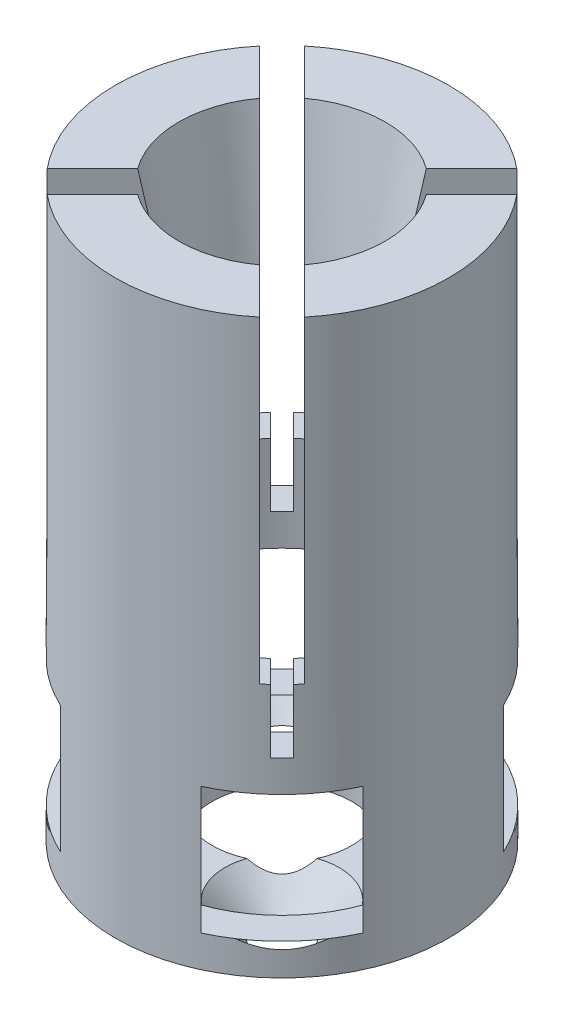
SolidWorks part; units mm, degrees
ref_plane "Front Plane" through (0, 0, 0) normal (0, 0, 1) x (1, 0, 0)
ref_plane "Top Plane" through (0, 0, 0) normal (0, 1, 0) x (1, 0, 0)
ref_plane "Right Plane" through (0, 0, 0) normal (1, 0, 0) x (0, 0, -1)
sketch "Sketch1" plane through (0, 0, 0) normal (0, 1, 0) x (1, 0, 0)
  circle A0 centre (0, 0) radius 16.6687
  dimension "D1" = 33.3375
extrude "Boss-Extrude1" add sketch "Sketch1" along normal blind 3.175 contours A0
sketch "Sketch2" plane through (0, 3.175, 0) normal (0, 1, 0) x (1, 0, 0)
  circle A0 centre (0, 0) radius 16.6687
  circle A1 centre (0, 0) radius 13.4938
  circle A2 centre (0, 0) radius 16.6687 construction
  dimension "D2" = 3.175
extrude "Boss-Extrude2" add sketch "Sketch2" along normal blind 53.975
ref_axis "Axis1" through (0, 57.15, 0) along (0, -1, 0)
ref_plane "Plane1" through (0, 0, 0) normal (-0.7071, 0, 0.7071) x (0, -1, 0)
ref_plane "Plane2" through (0, 31.75, 0) normal (0, 1, 0) x (1, 0, 0)
ref_plane "Plane3" through (0, 57.15, 0) normal (0, 1, 0) x (1, 0, 0)
sketch "Sketch7" plane through (0, 0, 0) normal (0, -1, 0) x (1, 0, 0)
  circle A0 centre (0, 0) radius 6.985
  dimension "D1" = 13.97
extrude "Cut-Extrude1" cut sketch "Sketch7" against normal through all
sketch "Sketch12" plane through (0, 31.75, 0) normal (0, 1, 0) x (1, 0, 0)
  circle A0 centre (0, 0) radius 14.2875
  dimension "D1" = 28.575
extrude "Boss-Extrude7" add sketch "Sketch12" along normal blind 25.4 contours A0
sketch "Sketch10" plane through (0, 57.15, 0) normal (0, 1, 0) x (1, 0, 0)
  circle A0 centre (0, 0) radius 10.32
  dimension "D1" = 20.64
sketch "Sketch11" plane through (0, 31.75, 0) normal (0, 1, 0) x (1, 0, 0)
  circle A0 centre (0, 0) radius 6.35
  dimension "D1" = 12.7
loft "Cut-Loft2" cut profiles "Sketch10", "Sketch11" connector at (-0.5056, 57.15, -10.3076) connector at (-3.3654, 31.75, -5.3849)
sketch "Sketch9" plane through (0, 0, 0) normal (-0.7071, 0, 0.7071) x (0, -1, 0)
  line L5 (-3.1775, -5.715) -> (-15.8775, -5.715)
  line L6 (-19.05, -0.8001) -> (-25.4, -0.8001)
  line L7 (-25.4, -1.5875) -> (-177.8, -1.5875)
  line L8 (-25.4, -1.5875) -> (-25.4, 1.5875)
  line L9 (-25.4, 1.5875) -> (-177.8, 1.5875)
  line L10 (-177.8, -1.5875) -> (-177.8, 1.5875)
  line L11 (-25.4, -1.5875) -> (-177.8, 1.5875) construction
  line L12 (-25.4, 1.5875) -> (-177.8, -1.5875) construction
  line L13 (-19.05, -0.8001) -> (-19.05, 0.8001)
  line L14 (-19.05, 0.8001) -> (-25.4, 0.8001)
  line L15 (-25.4, -0.8001) -> (-25.4, 0.8001)
  line L16 (-19.05, -0.8001) -> (-25.4, 0.8001) construction
  line L17 (-19.05, 0.8001) -> (-25.4, -0.8001) construction
  line L18 (-57.15, 0) -> (-3.175, 0) construction
  line L19 (-3.1775, -5.715) -> (-3.1775, 5.715)
  line L20 (-3.1775, 5.715) -> (-15.8775, 5.715)
  line L21 (-15.8775, -5.715) -> (-15.8775, 5.715)
  line L22 (-3.1775, -5.715) -> (-15.8775, 5.715) construction
  line L23 (-3.1775, 5.715) -> (-15.8775, -5.715) construction
  line L24 (0, -16.6688) -> (0, 16.6688) construction
  point P4 (-22.225, 0)
  point P9 (-101.6, 0)
  point P16 (-9.5275, 0)
  dimension "D1" = 3.175
  dimension "D2" = 25.4
  dimension "D3" = 1.6002
  dimension "D4" = 6.35
  dimension "D5" = 152.4
  dimension "D6" = 11.43
  dimension "D7" = 12.7
  dimension "D8" = 3.1775
extrude "Cut-Extrude2" cut sketch "Sketch9" against normal up to next contours L7 L10 L9 L8 | L6 L15 L14 L13 | L19 L5 L21 L20
pattern_circular "CirPattern2" count 4 over 360 about axis through (0, 0, 0) along (0, 1, 0) of "Cut-Extrude2"
sketch "Sketch5" plane through (0, 0, 0) normal (0, -1, 0) x (1, 0, 0)
  line L0 (-8.255, 8.255) -> (8.255, -8.255) construction
  line L1 (8.255, -8.255) -> (8.255, 8.255) construction
  line L2 (8.255, 8.255) -> (-8.255, -8.255) construction
  line L3 (-8.255, -8.255) -> (8.255, -8.255) construction
  line L4 (-8.255, -8.255) -> (-8.255, 8.255) construction
  line L5 (-8.255, 8.255) -> (8.255, 8.255) construction
  circle A0 centre (-8.255, 8.255) radius 2.5527
  circle A1 centre (8.255, 8.255) radius 2.5527
  circle A2 centre (8.255, -8.255) radius 2.5527
  circle A3 centre (-8.255, -8.255) radius 2.5527
  point P8 (0, 0)
  dimension "D1" = 5.1054
  dimension "D2" = 23.3487
sketch "Sketch6" plane through (0, 3.175, 0) normal (0, 1, 0) x (1, 0, 0)
  circle A0 centre (-8.255, 8.255) radius 5.715
  circle A1 centre (8.255, 8.255) radius 5.715
  circle A2 centre (8.255, -8.255) radius 5.715
  circle A3 centre (-8.255, -8.255) radius 5.715
  dimension "D4" = 11.43
loft "Cut-Loft1" cut section "Sketch5" section "Sketch6" connector at (5.7028, 0, -8.2069) connector at (2.54, 3.175, -8.273)
pattern_circular "CirPattern1" count 4 over 360 about axis through (0, 0, 0) along (0, 1, 0) of "Cut-Loft1"
